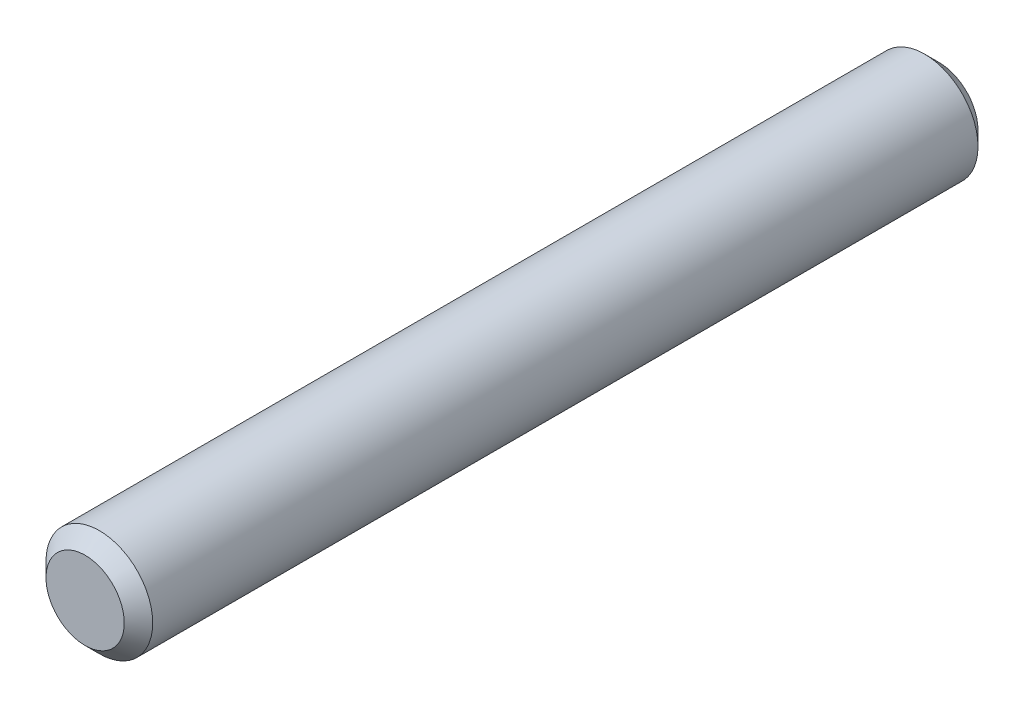
SolidWorks part; units mm, degrees
material "1.4000 (X6Cr13)"
ref_plane "Ebene vorne" through (0, 0, 0) normal (0, 0, 1) x (1, 0, 0)
ref_plane "Ebene oben" through (0, 0, 0) normal (0, 1, 0) x (1, 0, 0)
ref_plane "Ebene rechts" through (0, 0, 0) normal (1, 0, 0) x (0, 0, -1)
sketch "Skizze1" plane through (0, 0, 0) normal (0, 0, 1) x (1, 0, 0)
  circle A0 centre (0, 0) radius 0.75
  dimension "D1" = 1.5
extrude "Aufsatz-Linear austragen1" add sketch "Skizze1" along normal blind 6 and the other way blind 6
ref_axis "Achse1" through (0, 0, 11.4304) along (0, 0, -1)
chamfer "Fase1" distance 0.2 angle 45 2 edges at (0.75, 0, -6) (0.75, 0, 6)
